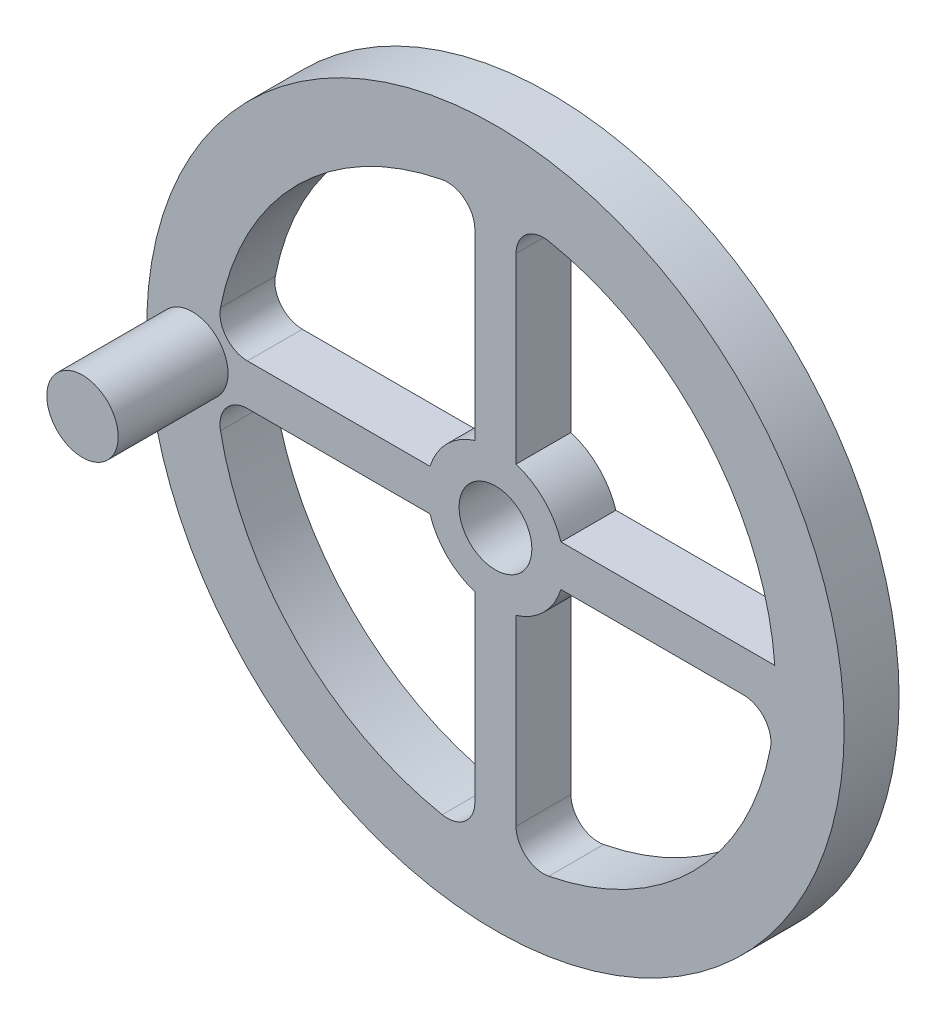
SolidWorks part; units mm, degrees
ref_plane "Front Plane" through (0, 0, 0) normal (0, 0, 1) x (1, 0, 0)
ref_plane "Top Plane" through (0, 0, 0) normal (0, 1, 0) x (1, 0, 0)
ref_plane "Right Plane" through (0, 0, 0) normal (1, 0, 0) x (0, 0, -1)
sketch "Sketch1" plane through (0, 0, 0) normal (0, 0, 1) x (1, 0, 0)
  line L0 (660.3835, -1256.5367) -> (647.0891, -1256.5367)
  line L2 (666.6532, -1239.9727) -> (666.6532, -1253.267)
  line L4 (663.6532, -1239.9727) -> (663.6532, -1253.267)
  line L7 (685.4979, -1256.5367) -> (669.9229, -1256.5367)
  line L9 (683.2172, -1259.5367) -> (669.9229, -1259.5367)
  line L16 (663.6532, -1262.8064) -> (663.6532, -1276.1008)
  line L17 (660.3835, -1259.5367) -> (647.0891, -1259.5367)
  line L21 (666.6532, -1262.8064) -> (666.6532, -1276.1008)
  circle A1 centre (665.1532, -1258.0367) radius 25.4
  arc A2 (647.0891, -1256.5367) -> (645.1256, -1254.1563) centre (647.0891, -1254.5367) cw
  arc A4 (661.2727, -1238.0092) -> (645.1256, -1254.1563) centre (665.1532, -1258.0367) ccw
  arc A5 (685.4979, -1256.5367) -> (669.0336, -1238.0092) centre (665.1532, -1258.0367) ccw
  arc A6 (669.0336, -1278.0643) -> (685.1807, -1261.9172) centre (665.1532, -1258.0367) ccw
  arc A7 (645.1256, -1261.9172) -> (661.2727, -1278.0643) centre (665.1532, -1258.0367) ccw
  arc A10 (663.6532, -1253.267) -> (660.3835, -1256.5367) centre (665.1532, -1258.0367) ccw
  circle A11 centre (665.1532, -1258.0367) radius 2.65
  arc A12 (660.3835, -1259.5367) -> (663.6532, -1262.8064) centre (665.1532, -1258.0367) ccw
  arc A13 (666.6532, -1262.8064) -> (669.9229, -1259.5367) centre (665.1532, -1258.0367) ccw
  arc A14 (669.9229, -1256.5367) -> (666.6532, -1253.267) centre (665.1532, -1258.0367) ccw
  arc A15 (669.0336, -1238.0092) -> (666.6532, -1239.9727) centre (668.6532, -1239.9727) ccw
  arc A16 (685.1807, -1261.9172) -> (683.2172, -1259.5367) centre (683.2172, -1261.5367) ccw
  arc A17 (669.0336, -1278.0643) -> (666.6532, -1276.1008) centre (668.6532, -1276.1008) cw
  arc A18 (663.6532, -1276.1008) -> (661.2727, -1278.0643) centre (661.6532, -1276.1008) cw
  arc A19 (645.1256, -1261.9172) -> (647.0891, -1259.5367) centre (647.0891, -1261.5367) cw
  arc A20 (663.6532, -1239.9727) -> (661.2727, -1238.0092) centre (661.6532, -1239.9727) ccw
  point P8 (666.6532, -1237.692)
  point P32 (644.8084, -1259.5367)
  dimension "D1" = 50.8
  dimension "D2" = 2
  dimension "D3" = 5
  dimension "D6" = 10
  dimension "D7" = 2
  dimension "D4" = 3
  dimension "D5" = 3
extrude "Boss-Extrude1" add sketch "Sketch1" along normal blind 4
sketch "Sketch2" plane through (0, 0, 4) normal (0, 0, 1) x (1, 0, 0)
  line L0 (639.7532, -1258.0367) -> (690.5532, -1258.0367) construction
  circle A0 centre (665.1532, -1258.0367) radius 25.4 construction
  circle A2 centre (643.0766, -1258.0367) radius 2.6
  dimension "D1" = 5.2
extrude "Boss-Extrude2" add sketch "Sketch2" along normal blind 8
